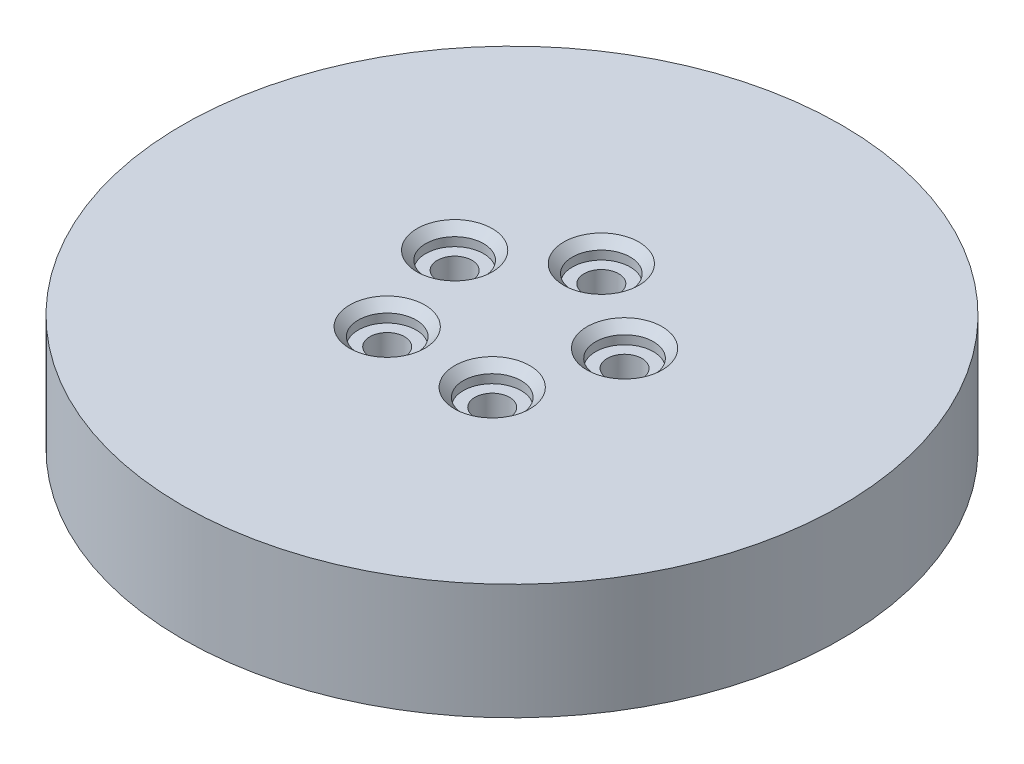
SolidWorks part; units mm, degrees
ref_plane "Front Plane" through (0, 0, 0) normal (0, 0, 1) x (1, 0, 0)
ref_plane "Top Plane" through (0, 0, 0) normal (0, 1, 0) x (1, 0, 0)
ref_plane "Right Plane" through (0, 0, 0) normal (1, 0, 0) x (0, 0, -1)
sketch "Sketch1" plane through (0, 0, 0) normal (0, 1, 0) x (1, 0, 0)
  circle A0 centre (0, 0) radius 114
  dimension "D1" = 228
extrude "Boss-Extrude1" add sketch "Sketch1" along normal blind 40
sketch "Sketch2" plane through (0, 40, 0) normal (0, 1, 0) x (1, 0, 0)
  line L1 (0, 30.9017) -> (-29.3893, 9.5492)
  line L2 (-29.3893, 9.5492) -> (-18.1636, -25)
  line L3 (-18.1636, -25) -> (18.1636, -25)
  line L4 (18.1636, -25) -> (29.3893, 9.5492)
  line L5 (29.3893, 9.5492) -> (0, 30.9017)
  circle A0 centre (0, 0) radius 25 construction
  circle A1 centre (0, 30.9017) radius 6
  circle A2 centre (-29.3893, 9.5492) radius 6
  circle A3 centre (-18.1636, -25) radius 6
  circle A4 centre (18.1636, -25) radius 6
  circle A5 centre (29.3893, 9.5492) radius 6
  dimension "D1" = 12
  dimension "D2" = 12
  dimension "D3" = 12
  dimension "D4" = 12
  dimension "D5" = 12
extrude "Cut-Extrude1" cut sketch "Sketch2" against normal blind 40 contours L1 A2 L2 | L2 A2 L1 | L1 A1 L5 | L5 A1 L1 | L5 A5 L4 | L4 A5 L5 | L3 A4 L4 | L4 A4 L3 | L2 A3 L3 | L3 A3 L2 region at (0, 40, -27.4681) region at (0, 40, -32.3732) region at (-26.1237, 40, -8.4881) region at (-30.7888, 40, -10.0039) region at (30.7888, 40, -10.0039) region at (26.1237, 40, -8.4881) region at (-16.1454, 40, 22.2222) region at (-19.0285, 40, 26.1905) region at (19.0285, 40, 26.1905) region at (16.1454, 40, 22.2222)
sketch "Sketch3" plane through (0, 0, 0) normal (0, -1, 0) x (1, 0, 0)
  circle A0 centre (0, 0) radius 45
  dimension "D1" = 90
extrude "Cut-Extrude2" cut sketch "Sketch3" against normal blind 15
sketch "Sketch4" plane through (0, 40, 0) normal (0, 1, 0) x (1, 0, 0)
  circle A5 centre (0, 30.9017) radius 10
  circle A6 centre (0, 30.9017) radius 10
  circle A8 centre (-29.3893, 9.5492) radius 10
  circle A9 centre (-29.3893, 9.5492) radius 10
  circle A11 centre (-18.1636, -25) radius 10
  circle A12 centre (-18.1636, -25) radius 10
  circle A14 centre (18.1636, -25) radius 10
  circle A15 centre (18.1636, -25) radius 10
  circle A17 centre (29.3893, 9.5492) radius 10
  circle A18 centre (29.3893, 9.5492) radius 10
  dimension "D1" = 4
  dimension "D2" = 4
  dimension "D3" = 4
  dimension "D4" = 4
  dimension "D5" = 4
extrude "Cut-Extrude3" cut sketch "Sketch4" against normal blind 6
chamfer "Chamfer1" distance 3 angle 45 5 edges at (-18.1636, 40, 35) (18.1636, 40, 35) (29.3893, 40, 0.4508) (-29.3893, 40, 0.4508) (0, 40, -20.9017)
